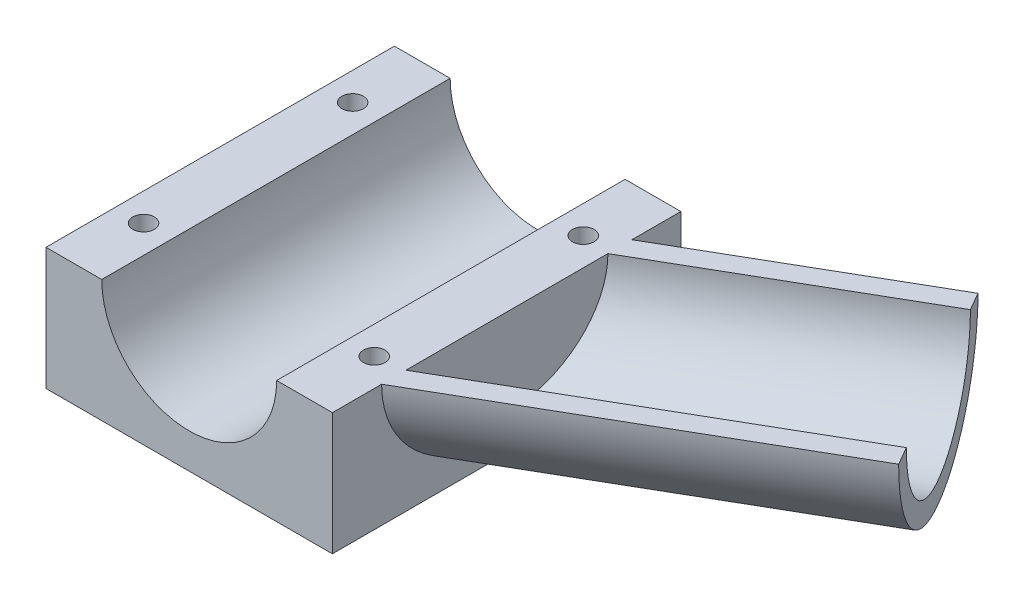
SolidWorks part; units mm, degrees
material "PLA"
ref_plane "Front Plane" through (0, 0, 0) normal (0, 0, 1) x (1, 0, 0)
ref_plane "Top Plane" through (0, 0, 0) normal (0, 1, 0) x (1, 0, 0)
ref_plane "Right Plane" through (0, 0, 0) normal (1, 0, 0) x (0, 0, -1)
sketch "Sketch1" plane through (0, 0, 0) normal (0, 0, 1) x (1, 0, 0)
  line L0 (-20.55, 17.55) -> (-20.55, 0)
  line L1 (55, 0) -> (-55, 0) construction
  line L2 (-20.55, 0) -> (20.55, 0)
  line L3 (20.55, 0) -> (20.55, 17.55)
  line L4 (-20.55, 17.55) -> (-12.55, 17.55)
  line L5 (20.55, 17.55) -> (12.55, 17.55)
  line L6 (0, -44.7868) -> (0, 44.7868) construction
  arc A0 (-12.55, 17.55) -> (12.55, 17.55) centre (0, 17.55) ccw
  dimension "D1" = 12.55
  dimension "D2" = 17.55
  dimension "D3" = 8
extrude "Boss-Extrude1" add sketch "Sketch1" along normal mid plane 50
sketch "Sketch2" plane through (0, 17.55, 0) normal (0, 1, 0) x (1, 0, 0)
  line L0 (-12.55, 25) -> (-20.55, 25) construction
  line L1 (-20.55, -25) -> (-20.55, 25) construction
  line L2 (12.55, -25) -> (12.55, 25) construction
  circle A0 centre (-16.55, 15) radius 1.55
  circle A1 centre (16.55, 15) radius 1.55
  circle A2 centre (16.55, -15) radius 1.55
  circle A3 centre (-16.55, -15) radius 1.55
  dimension "D1" = 3.1
  dimension "D2" = 30
  dimension "D3" = 10
  dimension "D4" = 4
  dimension "D5" = 4
extrude "Cut-Extrude1" cut sketch "Sketch2" against normal up to surface (17.55 mm away) up to face at (0, 0, 0)
sketch "Sketch4" plane through (0, 0, 0) normal (0, 1, 0) x (1, 0, 0)
  line L0 (20.4704, 0) -> (47.173, 15.4168) construction
  line L1 (-44.2539, 0) -> (44.2539, 0) construction
  line L2 (28.8644, 16.2947) -> (38.779, -0.8779) construction
  point P6 (33.8217, 7.7084)
  point P7 (33.8217, 7.7084)
  dimension "D1" = 30
ref_plane "LegBuildPlane" through (28.7041, 0, -16.5723) normal (0.866, 0, -0.5) x (-0.5, 0, -0.866)
sketch "Sketch5" plane through (28.7041, 0, -16.5723) normal (0.866, 0, -0.5) x (-0.5, 0, -0.866)
  line L0 (-25.805, 17.55) -> (-22.7852, 17.55)
  line L1 (2.3148, 17.55) -> (5.295, 17.55)
  line L2 (-0.3206, 0) -> (-20.1498, 0) construction
  arc A0 (-22.7852, 17.55) -> (2.3148, 17.55) centre (-10.2352, 17.55) ccw
  arc A1 (-25.805, 17.55) -> (5.295, 17.55) centre (-10.255, 17.55) ccw
  dimension "D1" = 15.55
  dimension "D2" = 12.55
  dimension "D3" = 17.55
  dimension "D4" = 0
extrude "Boss-Extrude2" add sketch "Sketch5" against normal up to surface and the other way blind 30 up to face at (20.55, 8.775, 0)
sketch "Sketch6" plane through (0, 17.55, 0) normal (0, 1, 0) x (1, 0, 0)
  line L0 (20.4704, 0) -> (47.173, 15.4168) construction
  line L1 (66.0774, 11.8398) -> (53.5274, 33.577) construction
  circle A0 centre (46.8121, 15.2084) radius 1.55
  dimension "D2" = 3.1
  dimension "D1" = 15
extrude "Cut-Extrude2" cut sketch "Sketch6" against normal up to surface (15.5297 mm away) up to face at (40.1812, 9.775, -11.3572)
equation "\"TubeDiam\" = 12.55"
equation "\"D1@Sketch1\"=\"TubeDiam\""
equation "\"D2@Sketch1\"=\"TubeDiam\"+5"
equation "\"MountLength\"=50"
equation "\"D1@Boss-Extrude1\"=\"MountLength\""
equation "\"MountHoleSize\"=3.1"
equation "\"D1@Sketch2\"=\"MountHoleSize\""
equation "\"D2@Sketch2\"=\"MountLength\"-20"
equation "\"LipWidth\"=8"
equation "\"D3@Sketch1\"=\"LipWidth\""
equation "\"D4@Sketch2\"=\"LipWidth\"/2"
equation "\"D5@Sketch2\"=\"LipWidth\"/2"
equation "\"LegDiam\"=12.55"
equation "\"D1@Sketch5\"=\"LegDiam\"+3"
equation "\"D2@Sketch5\"=\"TubeDiam\""
equation "\"D3@Sketch5\"=\"TubeDiam\"+5"
equation "\"D2@Sketch6\"=\"MountHoleSize\""
